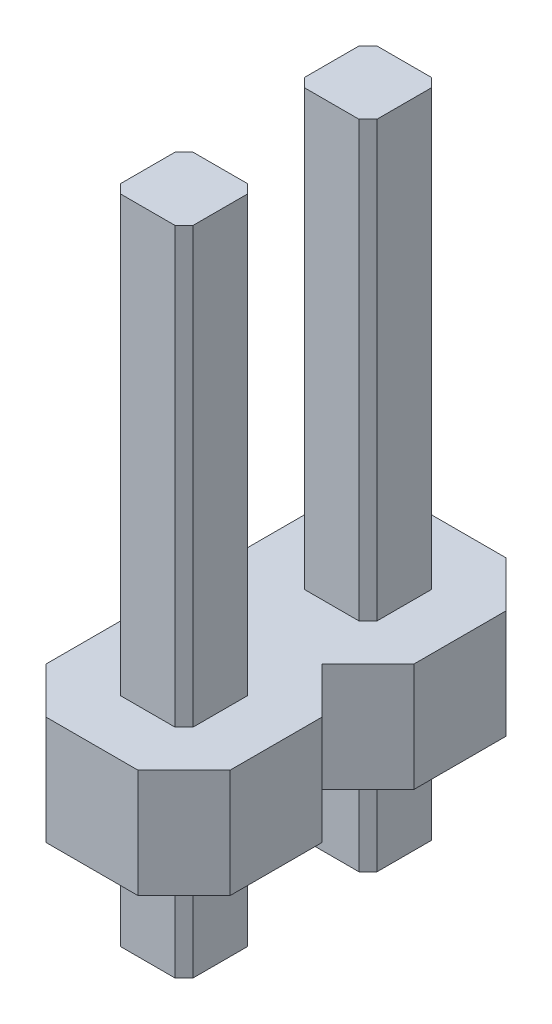
SolidWorks part; units mm, degrees
ref_plane "Plan de face" through (0, 0, 0) normal (0, 0, 1) x (1, 0, 0)
ref_plane "Plan de dessus" through (0, 0, 0) normal (0, 1, 0) x (1, 0, 0)
ref_plane "Plan de droite" through (0, 0, 0) normal (1, 0, 0) x (0, 0, -1)
sketch "Sketch1" plane through (0, 0, 0) normal (0, 1, 0) x (1, 0, 0)
  line L0 (-0.635, 10.16) -> (0.635, 10.16)
  line L1 (0.635, 10.16) -> (1.27, 9.525)
  line L2 (1.27, 9.525) -> (1.27, 8.255)
  line L3 (1.27, 8.255) -> (0.635, 7.62)
  line L4 (-0.635, 10.16) -> (-1.27, 9.525)
  line L5 (-1.27, 9.525) -> (-1.27, 8.255)
  line L6 (-1.27, 8.255) -> (-0.635, 7.62)
  line L7 (0.635, 7.62) -> (1.27, 6.985)
  line L8 (1.27, 6.985) -> (1.27, 5.715)
  line L9 (1.27, 5.715) -> (0.635, 5.08)
  line L10 (-0.635, 7.62) -> (-1.27, 6.985)
  line L11 (-1.27, 6.985) -> (-1.27, 5.715)
  line L12 (-1.27, 5.715) -> (-0.635, 5.08)
  line L13 (0.635, 5.08) -> (1.27, 4.445)
  line L14 (1.27, 4.445) -> (1.27, 3.175)
  line L15 (1.27, 3.175) -> (0.635, 2.54)
  line L16 (-0.635, 5.08) -> (-1.27, 4.445)
  line L17 (-1.27, 4.445) -> (-1.27, 3.175)
  line L18 (-1.27, 3.175) -> (-0.635, 2.54)
  line L19 (0.635, 2.54) -> (1.27, 1.905)
  line L20 (1.27, 1.905) -> (1.27, 0.635)
  line L21 (1.27, 0.635) -> (0.635, 0)
  line L22 (-0.635, 2.54) -> (-1.27, 1.905)
  line L23 (-1.27, 1.905) -> (-1.27, 0.635)
  line L24 (-1.27, 0.635) -> (-0.635, 0)
  line L25 (0.635, 0) -> (1.27, -0.635)
  line L26 (1.27, -0.635) -> (1.27, -1.905)
  line L27 (1.27, -1.905) -> (0.635, -2.54)
  line L28 (-0.635, 0) -> (-1.27, -0.635)
  line L29 (-1.27, -0.635) -> (-1.27, -1.905)
  line L30 (-1.27, -1.905) -> (-0.635, -2.54)
  line L31 (0.635, -2.54) -> (1.27, -3.175)
  line L32 (1.27, -3.175) -> (1.27, -4.445)
  line L33 (1.27, -4.445) -> (0.635, -5.08)
  line L34 (-0.635, -2.54) -> (-1.27, -3.175)
  line L35 (-1.27, -3.175) -> (-1.27, -4.445)
  line L36 (-1.27, -4.445) -> (-0.635, -5.08)
  line L50 (-0.635, 7.62) -> (0.635, 7.62) construction
  line L51 (0, 10.16) -> (0, 7.62) construction
  line L52 (-0.635, -5.08) -> (0.635, -5.08)
  point P0 (0, 8.89)
  point P1 (0, 8.89)
  point P54 (0, 8.89)
extrude "Boss-Extrude1" add sketch "Sketch1" along normal blind 1.5
sketch "Sketch3" plane through (0, 1.5, 0) normal (0, 1, 0) x (1, 0, 0)
  line L0 (-1.27, 8.89) -> (1.27, 8.89) construction
  line L1 (-1.27, 9.525) -> (-1.27, 8.255) construction
  line L2 (1.27, 8.255) -> (1.27, 9.525) construction
  line L3 (0.375, 9.39) -> (0.5, 9.265)
  line L4 (-0.375, 9.39) -> (0.375, 9.39)
  line L5 (-0.5, 9.265) -> (-0.5, 8.515)
  line L6 (-0.375, 8.39) -> (0.375, 8.39)
  line L7 (0.5, 9.265) -> (0.5, 8.515)
  line L8 (-0.5, 9.39) -> (0.5, 8.39) construction
  line L9 (-0.5, 8.39) -> (0.5, 9.39) construction
  line L10 (0.375, 8.39) -> (0.5, 8.515)
  line L11 (-0.5, 8.515) -> (-0.375, 8.39)
  line L12 (-0.5, 9.265) -> (-0.375, 9.39)
  line L13 (0.375, 6.85) -> (0.5, 6.725)
  line L14 (-0.375, 6.85) -> (0.375, 6.85)
  line L15 (-0.5, 6.725) -> (-0.5, 5.975)
  line L16 (-0.375, 5.85) -> (0.375, 5.85)
  line L17 (0.5, 6.725) -> (0.5, 5.975)
  line L18 (0.375, 5.85) -> (0.5, 5.975)
  line L19 (-0.5, 5.975) -> (-0.375, 5.85)
  line L20 (-0.5, 6.725) -> (-0.375, 6.85)
  line L21 (-1.27, 6.35) -> (1.27, 6.35) construction
  line L22 (-0.5, 6.85) -> (0.5, 5.85) construction
  line L23 (-0.5, 5.85) -> (0.5, 6.85) construction
  line L24 (0.375, 4.31) -> (0.5, 4.185)
  line L25 (-0.375, 4.31) -> (0.375, 4.31)
  line L26 (-0.5, 4.185) -> (-0.5, 3.435)
  line L27 (-0.375, 3.31) -> (0.375, 3.31)
  line L28 (0.5, 4.185) -> (0.5, 3.435)
  line L29 (0.375, 3.31) -> (0.5, 3.435)
  line L30 (-0.5, 3.435) -> (-0.375, 3.31)
  line L31 (-0.5, 4.185) -> (-0.375, 4.31)
  line L32 (-1.27, 3.81) -> (1.27, 3.81) construction
  line L33 (-0.5, 4.31) -> (0.5, 3.31) construction
  line L34 (-0.5, 3.31) -> (0.5, 4.31) construction
  line L35 (0.375, 1.77) -> (0.5, 1.645)
  line L36 (-0.375, 1.77) -> (0.375, 1.77)
  line L37 (-0.5, 1.645) -> (-0.5, 0.895)
  line L38 (-0.375, 0.77) -> (0.375, 0.77)
  line L39 (0.5, 1.645) -> (0.5, 0.895)
  line L40 (0.375, 0.77) -> (0.5, 0.895)
  line L41 (-0.5, 0.895) -> (-0.375, 0.77)
  line L42 (-0.5, 1.645) -> (-0.375, 1.77)
  line L43 (-1.27, 1.27) -> (1.27, 1.27) construction
  line L44 (-0.5, 1.77) -> (0.5, 0.77) construction
  line L45 (-0.5, 0.77) -> (0.5, 1.77) construction
  line L46 (0.375, -0.77) -> (0.5, -0.895)
  line L47 (-0.375, -0.77) -> (0.375, -0.77)
  line L48 (-0.5, -0.895) -> (-0.5, -1.645)
  line L49 (-0.375, -1.77) -> (0.375, -1.77)
  line L50 (0.5, -0.895) -> (0.5, -1.645)
  line L51 (0.375, -1.77) -> (0.5, -1.645)
  line L52 (-0.5, -1.645) -> (-0.375, -1.77)
  line L53 (-0.5, -0.895) -> (-0.375, -0.77)
  line L54 (-1.27, -1.27) -> (1.27, -1.27) construction
  line L55 (-0.5, -0.77) -> (0.5, -1.77) construction
  line L56 (-0.5, -1.77) -> (0.5, -0.77) construction
  line L57 (0.375, -3.31) -> (0.5, -3.435)
  line L58 (-0.375, -3.31) -> (0.375, -3.31)
  line L59 (-0.5, -3.435) -> (-0.5, -4.185)
  line L60 (-0.375, -4.31) -> (0.375, -4.31)
  line L61 (0.5, -3.435) -> (0.5, -4.185)
  line L62 (0.375, -4.31) -> (0.5, -4.185)
  line L63 (-0.5, -4.185) -> (-0.375, -4.31)
  line L64 (-0.5, -3.435) -> (-0.375, -3.31)
  line L65 (-1.27, -3.81) -> (1.27, -3.81) construction
  line L66 (-0.5, -3.31) -> (0.5, -4.31) construction
  line L67 (-0.5, -4.31) -> (0.5, -3.31) construction
  point P6 (0, 8.89)
  point P22 (0, 6.35)
  point P37 (0, 3.81)
  point P52 (0, 1.27)
  point P67 (0, -1.27)
  point P82 (0, -3.81)
  dimension "D1" = 1
  dimension "D2" = 1
  dimension "D3" = 6
extrude "Boss-Extrude2" add sketch "Sketch3" along normal blind 6 and the other way blind 3
sketch "Sketch4" plane through (0, 0, 0) normal (0, 1, 0) x (1, 0, 0)
  line L0 (0.635, 2.54) -> (-0.635, 2.54)
  line L1 (-0.635, 2.54) -> (-3.5513, 2.1454)
  line L2 (-3.5513, 2.1454) -> (-3.5513, -5.549)
  line L3 (-3.5513, -5.549) -> (3.5184, -6.3053)
  line L4 (3.5184, -6.3053) -> (3.5184, 1.3234)
  line L5 (3.5184, 1.3234) -> (0.635, 2.54)
extrude "Cut-Extrude1" cut sketch "Sketch4" against normal through all and the other way through all
sketch "Sketch5" plane through (0, 1.5, 0) normal (0, 1, 0) x (1, 0, 0)
  line L0 (-0.635, 7.62) -> (0.635, 7.62)
  line L1 (0.635, 7.62) -> (3.3047, 8.5367)
  line L2 (3.3047, 8.5367) -> (1.9698, 11.1324)
  line L3 (1.9698, 11.1324) -> (-2.5652, 11.1324)
  line L4 (-2.5652, 11.1324) -> (-2.5652, 10.8246)
  line L5 (-2.5652, 7.8957) -> (-2.5652, 10.8246)
  line L6 (-0.635, 7.62) -> (-2.5652, 7.8957)
extrude "Cut-Extrude2" cut sketch "Sketch5" against normal blind 6 and the other way blind 6
